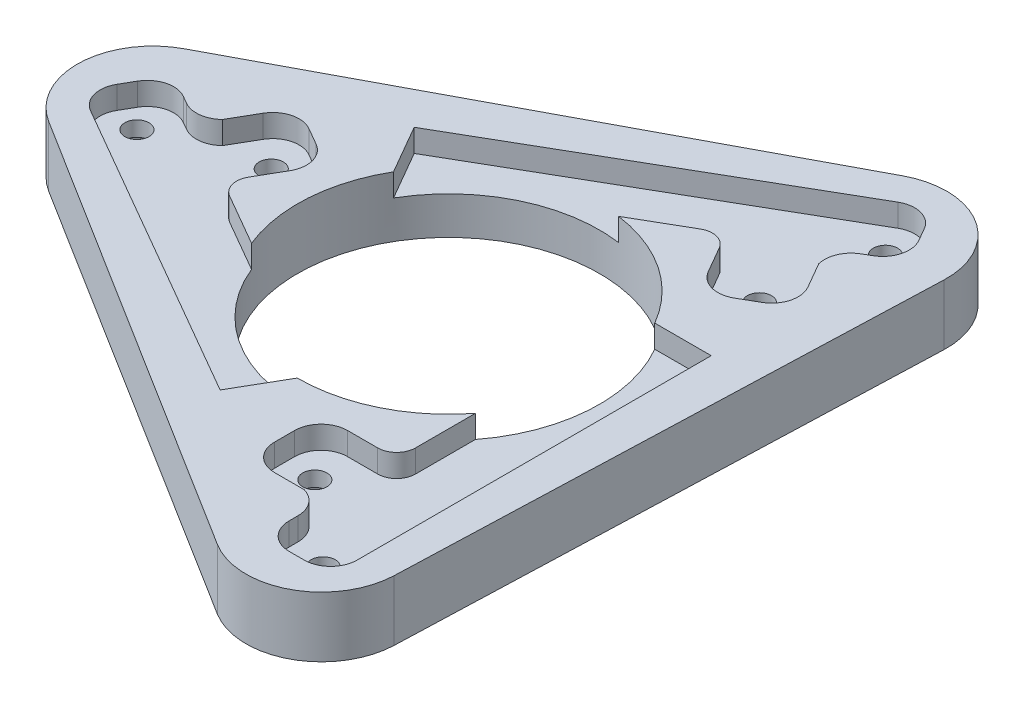
SolidWorks part; units mm, degrees
ref_plane "Plan de face" through (0, 0, 0) normal (0, 0, 1) x (1, 0, 0)
ref_plane "Plan de dessus" through (0, 0, 0) normal (0, 1, 0) x (1, 0, 0)
ref_plane "Plan de droite" through (0, 0, 0) normal (1, 0, 0) x (0, 0, -1)
sketch "Esquisse1" plane through (0, 0, 0) normal (0, 1, 0) x (1, 0, 0)
  line L7 (17.3205, 0) -> (-8.6603, 15) construction
  line L8 (-8.6603, 15) -> (-8.6603, -15) construction
  line L9 (-8.6603, -15) -> (17.3205, 0) construction
  circle A0 centre (0, 0) radius 8.6603 construction
  circle A1 centre (-8.6603, -15) radius 2 construction
  circle A2 centre (-8.6603, 15) radius 2 construction
  circle A3 centre (17.3205, 0) radius 2 construction
  dimension "D2" = 4
  dimension "D3" = 4
  dimension "D4" = 4
  dimension "D1" = 30
sketch "Esquisse4" plane through (0, 0, 0) normal (0, 1, 0) x (1, 0, 0)
  line L0 (17.7105, 7.28) -> (19.3105, 7.28) construction
  line L1 (19.3105, 7.28) -> (19.3105, -22.72) construction
  line L2 (19.3105, -22.72) -> (17.7105, -22.72) construction
  line L3 (17.7105, -22.72) -> (17.7105, 7.28) construction
  line L7 (-2.5506, -18.9777) -> (-28.5314, -3.9777) construction
  line L8 (-28.5314, -3.9777) -> (-29.3314, -5.3634) construction
  line L9 (-8.6603, 15) -> (-8.6603, -15) construction
  line L10 (-15.1599, 11.6977) -> (-15.9599, 13.0834) construction
  line L11 (-15.9599, 13.0834) -> (10.0208, 28.0834) construction
  line L12 (10.0208, 28.0834) -> (10.8208, 26.6977) construction
  line L13 (10.8208, 26.6977) -> (-15.1599, 11.6977) construction
  line L14 (-8.6603, -15) -> (17.3205, 0) construction
  line L15 (-29.3314, -5.3634) -> (-3.3506, -20.3634) construction
  line L16 (-3.3506, -20.3634) -> (-2.5506, -18.9777) construction
  point P2 (-29.2547, -5.2006)
  point P7 (36.8016, 11.6977)
  point P8 (9.5932, -1.1759)
  point P12 (15.7036, -7.0982)
  point P18 (0, 0)
  point P19 (-2.1696, 18.3266)
  point P22 (33.7427, -16.1274)
  point P23 (15.3294, 22.7201)
  point P24 (-15.8636, 12.7482)
  point P27 (17.7361, -22.7269)
  dimension "D2" = 1.6
  dimension "D3" = 30
  dimension "D4" = 7.28
  dimension "D5" = 0.39
  dimension "D6" = 60
  dimension "D7" = 0.39
  dimension "D8" = 1.6
  dimension "D9" = 1.6
  dimension "D10" = 0.39
  dimension "D11" = 7.28
  dimension "D12" = 30
  dimension "D13" = 1.6
  dimension "D14" = 7.28
  dimension "D15" = 30
  dimension "D16" = 1.6
  dimension "D17" = 60
sketch "Esquisse5" plane through (0, 0, 0) normal (0, 1, 0) x (1, 0, 0)
  line L1 (28.4325, -53.5405) -> (32.1512, 51.3936)
  line L2 (32.1512, 51.3936) -> (-60.5837, 2.147)
  line L3 (-60.5837, 2.147) -> (28.4325, -53.5405)
  circle A1 centre (0, 0) radius 20
  circle A2 centre (0, 0) radius 30.3109 construction
  dimension "D1" = 105
  dimension "D2" = 40
extrude "Boss.-Extru.1" add sketch "Esquisse5" along normal blind 8
ref_axis "Axe1" through (0, 130.0156, 0) along (0, -1, 0)
sketch "Esquisse8" plane through (0, 8, 0) normal (0, 1, 0) x (1, 0, 0)
  line L32 (-34.2314, 4.3938) -> (-32.2314, 7.8579) construction
  line L33 (-45.2217, 1.5015) -> (-44.2217, 3.2336) construction
  line L36 (-40.1237, 4.3317) -> (-39.1126, 3.7479) construction
  line L37 (-25.6333, -4.0344) -> (0.0494, -18.8623) construction
  line L40 (0.0494, -18.8623) -> (-3.9506, -25.7905) construction
  line L41 (-15.3769, -19.1935) -> (4.4757, -30.6554) construction
  line L52 (-3.9506, -25.7905) -> (0.0494, -18.8623) construction
  line L53 (-3.9506, -25.7905) -> (-44.1237, -2.5966) construction
  line L54 (-28.1333, 8.956) -> (-25.8294, 7.6259) construction
  line L55 (-24.7314, 3.5278) -> (-26.7314, 0.0637) construction
  line L56 (-26.7314, 0.0637) -> (-24.7314, 3.5278) construction
  line L57 (21.3877, 27.6397) -> (23.3539, 24.2342)
  line L58 (22.0728, 19.4531) -> (19.7689, 18.123)
  line L82 (-34.6305, 4.7025) -> (-32.6644, 8.1079)
  line L83 (-27.8833, 9.389) -> (-25.5794, 8.0589)
  line L84 (-24.2983, 3.2778) -> (-26.2983, -0.1863)
  line L85 (-25.3833, -3.6014) -> (0.7324, -18.6793)
  line L86 (0.7324, -18.6793) -> (-3.7676, -26.4735)
  line L87 (-3.7676, -26.4735) -> (-44.3737, -3.0296)
  line L88 (-45.6547, 1.7515) -> (-44.6547, 3.4836)
  line L89 (-39.8737, 4.7647) -> (-38.8626, 4.1809)
  line L90 (14.9878, 19.4041) -> (12.9878, 22.8682)
  line L91 (9.5728, 23.7832) -> (-16.5429, 8.7053)
  line L92 (-16.5429, 8.7053) -> (-21.0429, 16.4996)
  line L93 (-21.0429, 16.4996) -> (19.5631, 39.9435)
  line L94 (24.3442, 38.6624) -> (25.3442, 36.9304)
  line L95 (24.0631, 32.1493) -> (23.0521, 31.5656)
  line L96 (20.9208, 27.4483) -> (22.9208, 23.9842) construction
  line L97 (23.9112, 38.4124) -> (24.9112, 36.6804) construction
  line L98 (23.8131, 32.5823) -> (22.8021, 31.9986) construction
  line L99 (9.3228, 24.2163) -> (-16.3599, 9.3883) construction
  line L100 (-16.3599, 9.3883) -> (-20.3599, 16.3166) construction
  line L101 (-20.3599, 16.3166) -> (19.8131, 39.5105) construction
  line L102 (21.8228, 19.8861) -> (19.5189, 18.556) construction
  line L103 (15.4208, 19.6541) -> (13.4208, 23.1182) construction
  line L104 (13.2428, -32.3421) -> (9.3105, -32.3421)
  line L105 (5.8105, -28.8421) -> (5.8105, -26.1819)
  line L106 (9.3105, -22.6819) -> (13.3105, -22.6819)
  line L107 (15.8105, -20.1819) -> (15.8105, 9.9739)
  line L108 (15.8105, 9.9739) -> (24.8105, 9.9739)
  line L109 (24.8105, 9.9739) -> (24.8105, -36.9139)
  line L110 (21.3105, -40.4139) -> (19.3105, -40.4139)
  line L111 (15.8105, -36.9139) -> (15.8105, -35.7465)
  line L112 (13.3105, -31.8421) -> (9.3105, -31.8421) construction
  line L113 (21.3105, -39.9139) -> (19.3105, -39.9139) construction
  line L114 (16.3105, -36.9139) -> (16.3105, -35.7465) construction
  line L115 (16.3105, -20.1819) -> (16.3105, 9.4739) construction
  line L116 (16.3105, 9.4739) -> (24.3105, 9.4739) construction
  line L117 (24.3105, 9.4739) -> (24.3105, -36.9139) construction
  line L118 (6.3105, -28.8421) -> (6.3105, -26.1819) construction
  line L119 (9.3105, -23.1819) -> (13.3105, -23.1819) construction
  arc A8 (-44.1237, -2.5966) -> (-45.2217, 1.5015) centre (-42.6237, 0.0015) cw construction
  arc A10 (-44.2217, 3.2336) -> (-40.1237, 4.3317) centre (-41.6237, 1.7336) cw construction
  arc A11 (-39.1126, 3.7479) -> (-34.2314, 4.3938) centre (-37.0923, 7.2473) ccw construction
  arc A12 (-26.7314, 0.0637) -> (-27.1307, -1.3112) centre (-24.1333, -1.4363) ccw construction
  arc A13 (-32.2314, 7.8579) -> (-28.1333, 8.956) centre (-29.6333, 6.3579) cw construction
  arc A14 (-25.8294, 7.6259) -> (-24.7314, 3.5278) centre (-27.3294, 5.0278) cw construction
  arc A15 (-26.7314, 0.0637) -> (-25.6333, -4.0344) centre (-24.1333, -1.4363) ccw construction
  arc A28 (-32.6644, 8.1079) -> (-27.8833, 9.389) centre (-29.6333, 6.3579) cw
  arc A29 (-25.5794, 8.0589) -> (-24.2983, 3.2778) centre (-27.3294, 5.0278) cw
  arc A30 (-26.2983, -0.1863) -> (-25.3833, -3.6014) centre (-24.1333, -1.4363) ccw
  arc A31 (-44.3737, -3.0296) -> (-45.6547, 1.7515) centre (-42.6237, 0.0015) cw
  arc A32 (-44.6547, 3.4836) -> (-39.8737, 4.7647) centre (-41.6237, 1.7336) cw
  arc A33 (-38.8626, 4.1809) -> (-34.6305, 4.7025) centre (-37.0923, 7.2473) ccw
  arc A34 (23.3539, 24.2342) -> (22.0728, 19.4531) centre (20.3228, 22.4842) cw
  arc A35 (19.7689, 18.123) -> (14.9878, 19.4041) centre (18.0189, 21.1541) cw
  arc A36 (12.9878, 22.8682) -> (9.5728, 23.7832) centre (10.8228, 21.6182) ccw
  arc A37 (19.5631, 39.9435) -> (24.3442, 38.6624) centre (21.3131, 36.9124) cw
  arc A38 (25.3442, 36.9304) -> (24.0631, 32.1493) centre (22.3131, 35.1804) cw
  arc A39 (23.0521, 31.5656) -> (21.3877, 27.6397) centre (24.8225, 28.4992) ccw
  arc A40 (19.8131, 39.5105) -> (23.9112, 38.4124) centre (21.3131, 36.9124) cw construction
  arc A41 (24.9112, 36.6804) -> (23.8131, 32.5823) centre (22.3131, 35.1804) cw construction
  arc A42 (22.8021, 31.9986) -> (20.9208, 27.4483) centre (24.8225, 28.4992) ccw construction
  arc A43 (22.9208, 23.9842) -> (21.8228, 19.8861) centre (20.3228, 22.4842) cw construction
  arc A44 (19.5189, 18.556) -> (15.4208, 19.6541) centre (18.0189, 21.1541) cw construction
  arc A45 (13.4208, 23.1182) -> (9.3228, 24.2163) centre (10.8228, 21.6182) ccw construction
  arc A46 (9.3105, -32.3421) -> (5.8105, -28.8421) centre (9.3105, -28.8421) cw
  arc A47 (5.8105, -26.1819) -> (9.3105, -22.6819) centre (9.3105, -26.1819) cw
  arc A48 (13.3105, -22.6819) -> (15.8105, -20.1819) centre (13.3105, -20.1819) ccw
  arc A49 (24.8105, -36.9139) -> (21.3105, -40.4139) centre (21.3105, -36.9139) cw
  arc A50 (19.3105, -40.4139) -> (15.8105, -36.9139) centre (19.3105, -36.9139) cw
  arc A51 (15.8105, -35.7465) -> (13.2428, -32.3421) centre (12.2698, -35.7465) ccw
  arc A52 (24.3105, -36.9139) -> (21.3105, -39.9139) centre (21.3105, -36.9139) cw construction
  arc A53 (19.3105, -39.9139) -> (16.3105, -36.9139) centre (19.3105, -36.9139) cw construction
  arc A54 (16.3105, -35.7465) -> (13.3105, -31.8421) centre (12.2698, -35.7465) ccw construction
  arc A55 (9.3105, -31.8421) -> (6.3105, -28.8421) centre (9.3105, -28.8421) cw construction
  arc A56 (6.3105, -26.1819) -> (9.3105, -23.1819) centre (9.3105, -26.1819) cw construction
  arc A57 (13.3105, -23.1819) -> (16.3105, -20.1819) centre (13.3105, -20.1819) ccw construction
  point P91 (0, 0)
  point P108 (0, 0)
  point P149 (0, 0)
  point P150 (0, 0)
  dimension "D2" = 3
  dimension "D1" = 0.5
extrude "Enlèv. mat.-Extru.1" cut sketch "Esquisse8" against normal blind 3
hole_wizard "Dégagement M32" positions "Esquisse13" profile "Esquisse14" hole size "M3" standard "Ansi Metric" end condition through all
sketch "Esquisse13" plane through (0, 5, 0) normal (0, 1, 0) x (1, 0, 0)
  line L0 (24.3105, -36.9139) -> (16.3105, -36.9139) construction
  point P9 (-42.1237, 0.8675)
  point P12 (-28.7314, 5.2599)
  point P15 (18.9208, 22.2522)
  point P18 (21.8131, 36.0464)
  point P21 (9.8105, -27.512)
  point P27 (20.3105, -36.9139)
sketch "Esquisse14" plane through (-42.1237, 5, -0.8675) normal (1, 0, 0) x (0, 0, 1)
  line L0 (0, 0) -> (0, 5)
  line L1 (0, 5) -> (1.6, 5)
  line L2 (1.6, 5) -> (1.6, 0)
  line L5 (1.6, 0) -> (0, 0)
  line L11 (0, -6.35) -> (0, 107.95) construction
  dimension "Diamètre du perçage jusqu'au prochain" = 3.2
  dimension "Profondeur du perçage jusqu'au prochain" = 5
sketch "Esquisse15" plane through (0, 0, 0) normal (0, -1, 0) x (-1, 0, 0)
  line L0 (-6.3105, -27.512) -> (-13.3105, -27.512) construction
  line L1 (40.1117, -1.6633) -> (43.3094, -2.1403)
  line L2 (43.3094, -2.1403) -> (45.3214, 0.3905)
  line L3 (45.3214, 0.3905) -> (44.1356, 3.3984)
  line L4 (44.1356, 3.3984) -> (40.9379, 3.8754)
  line L5 (40.9379, 3.8754) -> (38.9259, 1.3446)
  line L6 (38.9259, 1.3446) -> (40.1117, -1.6633)
  line L7 (-24.4115, 34.1224) -> (-21.4461, 32.8341)
  line L8 (-21.4461, 32.8341) -> (-18.8477, 34.7581)
  line L9 (-18.8477, 34.7581) -> (-19.2148, 37.9704)
  line L10 (-19.2148, 37.9704) -> (-22.1802, 39.2586)
  line L11 (-22.1802, 39.2586) -> (-24.7786, 37.3347)
  line L12 (-24.7786, 37.3347) -> (-24.4115, 34.1224)
  line L13 (-23.2358, -38.291) -> (-20.5806, -40.1358)
  line L14 (-20.5806, -40.1358) -> (-17.6553, -38.7588)
  line L15 (-17.6553, -38.7588) -> (-17.3853, -35.5369)
  line L16 (-17.3853, -35.5369) -> (-20.0404, -33.6921)
  line L17 (-20.0404, -33.6921) -> (-22.9657, -35.0691)
  line L18 (-22.9657, -35.0691) -> (-23.2358, -38.291)
  line L19 (-6.5773, -27.512) -> (-8.1939, -24.712)
  line L20 (-8.1939, -24.712) -> (-11.4271, -24.712)
  line L21 (-11.4271, -24.712) -> (-13.0437, -27.512)
  line L22 (-13.0437, -27.512) -> (-11.4271, -30.312)
  line L23 (-11.4271, -30.312) -> (-8.1939, -30.312)
  line L24 (-8.1939, -30.312) -> (-6.5773, -27.512)
  line L26 (31.8809, 4.5292) -> (30.9389, 7.6221)
  line L27 (30.9389, 7.6221) -> (27.7893, 8.3527)
  line L28 (27.7893, 8.3527) -> (25.5818, 5.9905)
  line L29 (25.5818, 5.9905) -> (26.5238, 2.8976)
  line L30 (26.5238, 2.8976) -> (29.6734, 2.167)
  line L31 (29.6734, 2.167) -> (31.8809, 4.5292)
  line L32 (-15.7713, 22.9828) -> (-17.9788, 25.345)
  line L33 (-17.9788, 25.345) -> (-21.1284, 24.6144)
  line L34 (-21.1284, 24.6144) -> (-22.0704, 21.5215)
  line L35 (-22.0704, 21.5215) -> (-19.8629, 19.1593)
  line L36 (-19.8629, 19.1593) -> (-16.7133, 19.8899)
  line L37 (-16.7133, 19.8899) -> (-15.7713, 22.9828)
  circle A0 centre (42.1237, 0.8675) radius 2.8 construction
  circle A1 centre (-21.8131, 36.0464) radius 2.8 construction
  circle A2 centre (-20.3105, -36.9139) radius 2.8 construction
  circle A3 centre (-9.8105, -27.512) radius 2.8 construction
  circle A4 centre (28.7314, 5.2599) radius 2.8 construction
  circle A5 centre (-18.9208, 22.2522) radius 2.8 construction
  point P50 (-9.8105, -24.712)
  point P59 (28.0986, 2.5323)
  dimension "D1" = 5.6
  dimension "D2" = 5.6
  dimension "D3" = 5.6
  dimension "D4" = 5.6
  dimension "D5" = 5.6
  dimension "D6" = 5.6
extrude "Enlèv. mat.-Extru.3" cut sketch "Esquisse15" against normal blind 3
fillet "Congé1" radius 10 3 edges at (32.1512, 4, -51.3936) (28.4325, 4, 53.5405) (-60.5837, 4, -2.147)
